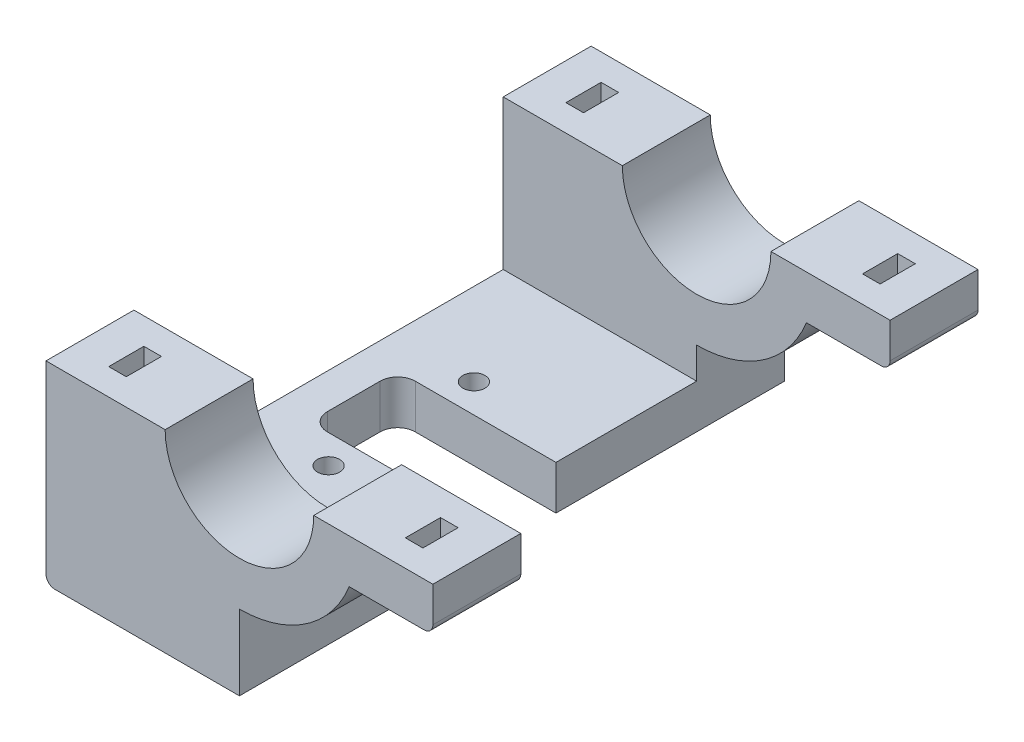
SolidWorks part; units mm, degrees
ref_plane "Front Plane" through (0, 0, 0) normal (0, 0, 1) x (1, 0, 0)
ref_plane "Top Plane" through (0, 0, 0) normal (0, 1, 0) x (1, 0, 0)
ref_plane "Right Plane" through (0, 0, 0) normal (1, 0, 0) x (0, 0, -1)
sketch "Sketch2" plane through (0, 0, 0) normal (0, 0, 1) x (1, 0, 0)
  line L0 (-27.94, 0) -> (-10.7315, 0)
  line L1 (-27.94, 0) -> (-27.94, -27.94)
  line L2 (-27.94, -27.94) -> (27.94, -27.94)
  line L3 (27.94, -27.94) -> (27.94, 0)
  line L4 (10.7315, 0) -> (27.94, 0)
  line L5 (0, 0) -> (10.7315, 0) construction
  arc A0 (-10.7315, 0) -> (10.7315, 0) centre (0, 0) ccw
  point P6 (0, 0)
  dimension "D1" = 21.463
  dimension "D2" = 55.88
  dimension "D3" = 27.94
  dimension "D4" = 27.94
extrude "Boss-Extrude1" add sketch "Sketch2" along normal blind 12.7
sketch "Sketch3" plane through (0, 0, 0) normal (0, 1, 0) x (1, 0, 0)
  line L0 (-27.94, -6.35) -> (27.94, -6.35) construction
  line L2 (-27.94, -12.7) -> (-27.94, 0) construction
  line L3 (-22.6931, -8.89) -> (-20.1531, -8.89)
  line L4 (27.94, -12.7) -> (27.94, 0) construction
  line L5 (-22.6931, -8.89) -> (-22.6931, -3.81)
  line L6 (-22.6931, -3.81) -> (-20.1531, -3.81)
  line L7 (-20.1531, -8.89) -> (-20.1531, -3.81)
  line L8 (-22.6931, -8.89) -> (-20.1531, -3.81) construction
  line L9 (-22.6931, -3.81) -> (-20.1531, -8.89) construction
  line L10 (22.6931, -8.89) -> (20.1531, -8.89)
  line L11 (22.6931, -8.89) -> (22.6931, -3.81)
  line L12 (22.6931, -3.81) -> (20.1531, -3.81)
  line L13 (20.1531, -8.89) -> (20.1531, -3.81)
  line L14 (22.6931, -8.89) -> (20.1531, -3.81) construction
  line L15 (22.6931, -3.81) -> (20.1531, -8.89) construction
  point P0 (-21.4231, -6.35)
  point P10 (21.4231, -6.35)
  dimension "D1" = 42.8462
  dimension "D2" = 21.4231
  dimension "D3" = 2.54
  dimension "D4" = 5.08
extrude "Cut-Extrude1" cut sketch "Sketch3" against normal through all
sketch "Sketch4" plane through (0, 0, 12.7) normal (0, 0, 1) x (1, 0, 0)
  line L0 (27.94, -27.94) -> (27.94, 0) construction
  line L1 (-27.94, -27.94) -> (27.94, -27.94)
  line L2 (-27.94, -27.94) -> (-27.94, -21.59)
  line L3 (-27.94, -21.59) -> (27.94, -21.59)
  line L4 (27.94, -27.94) -> (27.94, -21.59)
  dimension "D1" = 6.35
extrude "Boss-Extrude2" add sketch "Sketch4" along normal blind 26.67
ref_plane "Plane1" through (0, 0, 39.37) normal (0, 0, 1) x (1, 0, 0)
mirror "Mirror1" about plane through (0, 0, 39.37) normal (0, 0, -1) of bodies 103
sketch "Sketch5" plane through (0, -21.59, 0) normal (0, 1, 0) x (1, 0, 0)
  line L0 (-27.94, -39.37) -> (27.94, -39.37) construction
  line L3 (-22.86, -33.02) -> (8.89, -33.02)
  line L5 (-22.86, -45.7195) -> (8.89, -45.7195)
  line L9 (-27.94, -66.04) -> (-27.94, -12.7) construction
  line L10 (27.94, -66.04) -> (27.94, -12.7) construction
  line L11 (-27.94, -60.8397) -> (-27.94, -33.02) construction
  line L14 (-16.002, -49.87) -> (-16.002, -28.87) construction
  line L15 (0, -12.7) -> (0, -66.04) construction
  line L16 (27.94, -12.7) -> (-27.94, -12.7) construction
  line L17 (10.7315, -66.04) -> (-10.7315, -66.04) construction
  line L18 (8.89, -33.02) -> (8.89, -45.7195)
  line L19 (-22.86, -33.02) -> (-22.86, -45.7195)
  circle A1 centre (-16.002, -28.87) radius 1.6
  circle A2 centre (-16.002, -49.87) radius 1.6
  dimension "D9" = 3.2
  dimension "D2" = 6.35
  dimension "D3" = 12.6995
  dimension "D4" = 31.75
  dimension "D5" = 5.08
  dimension "D10" = 21
  dimension "D11" = 10.5
  dimension "D12" = 16.002
extrude "Cut-Extrude3" cut sketch "Sketch5" against normal through all
sketch "Sketch7" plane through (0, 0, 78.74) normal (0, 0, 1) x (1, 0, 0)
  line L1 (0, -17.0815) -> (0, -27.94)
  line L2 (15.8573, -6.35) -> (27.94, -6.35)
  line L3 (15.8573, -6.35) -> (27.94, -6.35)
  line L4 (-27.94, -27.94) -> (27.94, -27.94) construction
  line L5 (27.94, -6.35) -> (27.94, -27.94)
  line L6 (27.94, -27.94) -> (0, -27.94)
  arc A3 (-17.0815, 0) -> (15.8573, -6.35) centre (0, 0) ccw
  arc A4 (0, -17.0815) -> (15.8573, -6.35) centre (0, 0) ccw
  dimension "D1" = 6.35
extrude "Cut-Extrude4" cut sketch "Sketch7" against normal up to surface (78.74 mm away) up to face at (0, -11.1019, 0)
fillet "Fillet1" radius 1.27 7 edges at (-22.6931, -27.94, 72.39) (-27.94, -27.94, 39.37) (-22.6931, -27.94, 6.35) (22.6931, -6.35, 6.35) (27.94, -6.35, 6.35) (27.94, -6.35, 72.39) (22.6931, -6.35, 72.39)
fillet "Fillet2" radius 2.54 2 edges at (-22.86, -24.765, 45.7195) (-22.86, -24.765, 33.02)
